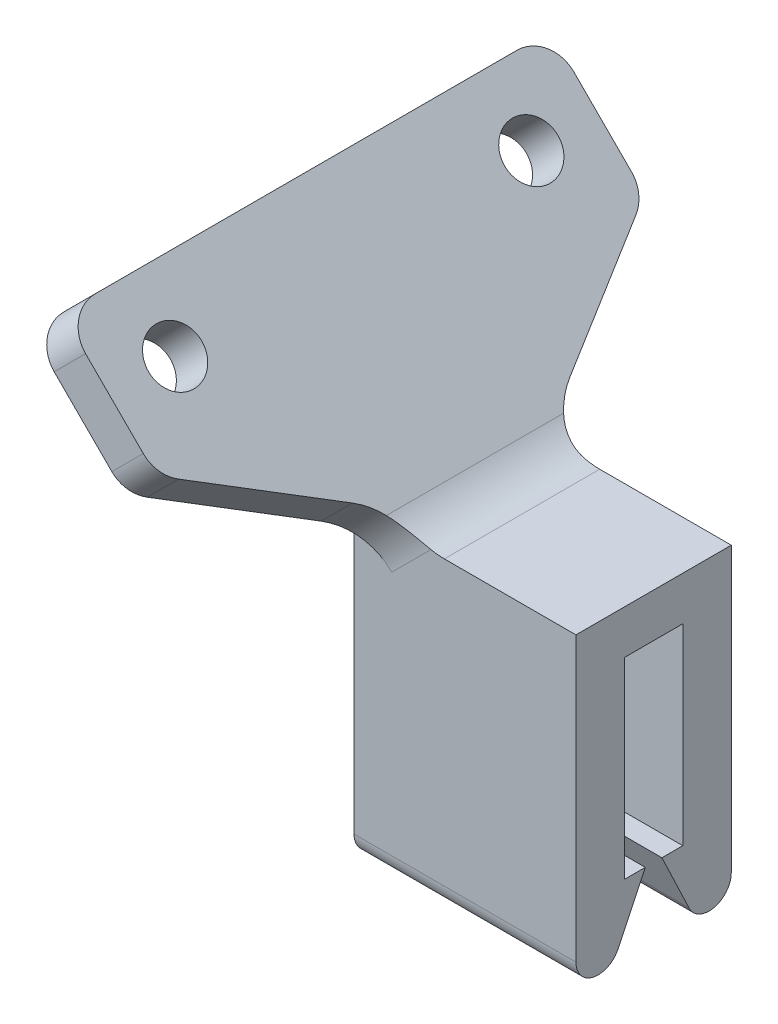
SolidWorks part; units mm, degrees
ref_plane "Front Plane" through (0, 0, 0) normal (0, 0, 1) x (1, 0, 0)
ref_plane "Top Plane" through (0, 0, 0) normal (0, 1, 0) x (1, 0, 0)
ref_plane "Right Plane" through (0, 0, 0) normal (1, 0, 0) x (0, 0, -1)
sketch "Sketch1" plane through (0, 0, 0) normal (1, 0, 0) x (0, 0, -1)
  line L0 (-0.375, -4.33) -> (0.375, -4.33) construction
  line L1 (-1.315, 4.33) -> (1.315, 4.33)
  line L2 (-1.315, 4.33) -> (-1.315, -4.33)
  line L3 (-1.315, -4.33) -> (1.315, -4.33) construction
  line L4 (1.315, 4.33) -> (1.315, -4.33)
  line L5 (-1.315, 4.33) -> (1.315, -4.33) construction
  line L6 (-1.315, -4.33) -> (1.315, 4.33) construction
  line L7 (-0.375, -4.33) -> (-1.315, -4.33)
  line L8 (0.375, -4.33) -> (1.315, -4.33)
  line L9 (-1.315, -4.33) -> (-1.315, -6.305) construction
  line L10 (1.315, -4.33) -> (1.315, -6.3107) construction
  line L11 (1.315, -6.3107) -> (0.375, -4.33)
  line L12 (-1.315, -6.305) -> (-0.375, -4.33)
  line L13 (0, 4.33) -> (0, 6.305) construction
  line L14 (-3.5, 6.305) -> (3.5, 6.305)
  line L15 (-3.5, 6.305) -> (-3.5, -6.4679)
  line L16 (-1.5971, -6.8976) -> (-1.315, -6.305)
  line L17 (1.315, -6.3107) -> (1.5966, -6.9041)
  line L18 (3.5, -6.4753) -> (3.5, 6.305)
  arc A0 (1.5966, -6.9041) -> (3.5, -6.4753) centre (2.5, -6.4753) ccw
  arc A1 (-3.5, -6.4679) -> (-1.5971, -6.8976) centre (-2.5, -6.4679) ccw
  point P0 (0, 0)
  point P9 (0, -4.33)
  point P16 (0, 6.305)
  dimension "D3" = 1
  dimension "D1" = 7
  dimension "D2" = 0.75
extrude "Boss-Extrude1" add sketch "Sketch1" along normal blind 10 contours L4 L8 L11 L17 A0 L18 L14 L15 A1 L16 L12 L7 L2 L1
sketch "Sketch4" plane through (0, 0, 0) normal (0, 0, 1) x (1, 0, 0)
  line L0 (0, 6.305) -> (-7.0711, 13.3761)
  line L1 (-7.0711, 13.3761) -> (-5.6569, 14.7903)
  line L2 (-5.6569, 14.7903) -> (2.8284, 6.305)
  line L3 (10, 6.305) -> (0, 6.305) construction
  line L4 (2.8284, 6.305) -> (0, 6.305)
extrude "Boss-Extrude3" add sketch "Sketch4" along normal up to surface and the other way up to surface up to face at (5, -0.0814, 3.5) other way up to face at (5, -0.0852, -3.5)
fillet "Fillet1" radius 3 1 edges at (0, 6.305, 0)
fillet "Fillet2" radius 3 1 edges at (2.8284, 6.305, 0)
sketch "Sketch5" plane through (4.5667, 4.5667, 0) normal (0.7071, 0.7071, 0) x (0, 0, -1)
  line L0 (0, 14.4583) -> (0, 11.4583) construction
  line L1 (-3.5, 14.4583) -> (3.5, 14.4583) construction
  line L2 (-8.025, 11.4583) -> (8.025, 11.4583) construction
  line L3 (-9.5, 14.4583) -> (9.5, 14.4583)
  line L4 (-11, 12.9583) -> (-11, 9.2832)
  line L5 (-10.3035, 8.0165) -> (-3.5, 3.7009)
  line L6 (-3.5, 3.7009) -> (3.5, 3.7009)
  line L7 (11, 12.9583) -> (11, 9.2832)
  line L8 (10.3035, 8.0165) -> (3.5, 3.7009)
  circle A0 centre (-8.025, 11.4583) radius 1.2
  circle A1 centre (8.025, 11.4583) radius 1.2
  arc A2 (11, 9.2832) -> (10.3035, 8.0165) centre (9.5, 9.2832) cw
  arc A3 (9.5, 14.4583) -> (11, 12.9583) centre (9.5, 12.9583) cw
  arc A4 (-9.5, 14.4583) -> (-11, 12.9583) centre (-9.5, 12.9583) ccw
  arc A5 (-11, 9.2832) -> (-10.3035, 8.0165) centre (-9.5, 9.2832) ccw
  point P8 (0, 11.4583)
  point P15 (0, 14.4583)
  dimension "D1" = 1.5
extrude "Boss-Extrude4" add sketch "Sketch5" against normal up to surface (2 mm away) up to face at (-3.9749, 10.2799, 0)
fillet "Fillet3" radius 3 2 edges at (1.2426, 6.4766, -3.5) (1.2426, 6.4766, 3.5)
